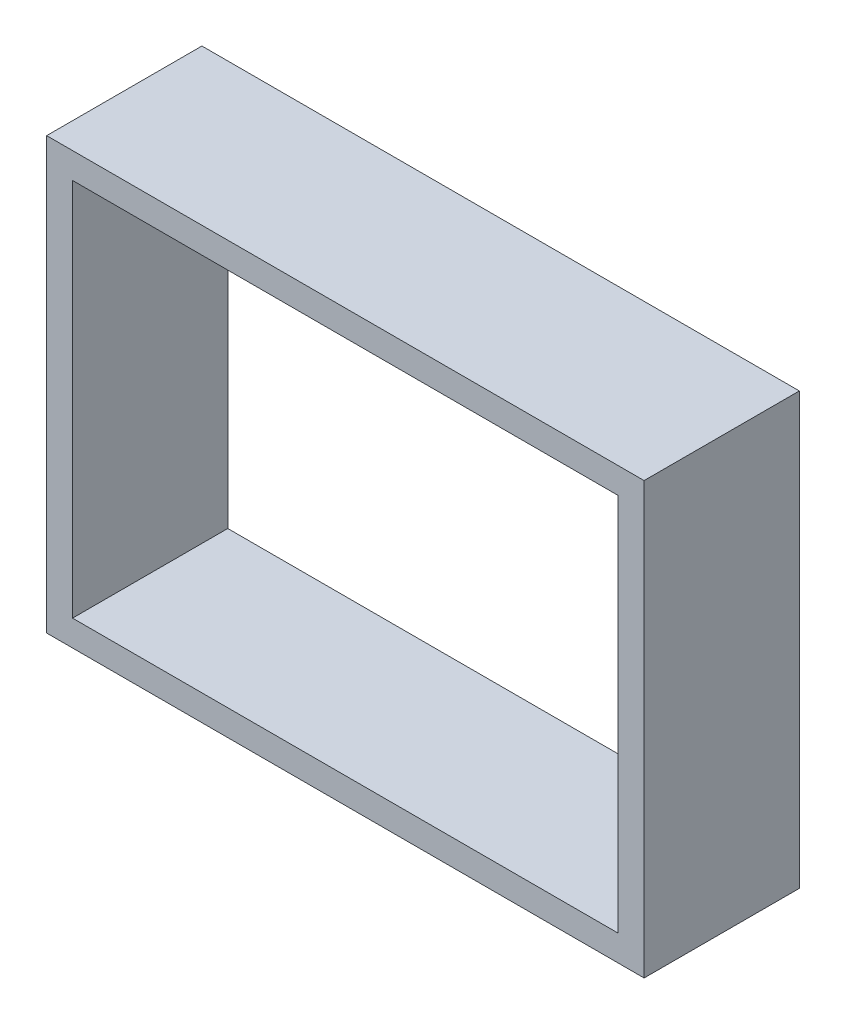
SolidWorks part; units mm, degrees
ref_plane "Alzado" through (0, 0, 0) normal (0, 0, 1) x (1, 0, 0)
ref_plane "Planta" through (0, 0, 0) normal (0, 1, 0) x (1, 0, 0)
ref_plane "Vista lateral" through (0, 0, 0) normal (1, 0, 0) x (0, 0, -1)
sketch "Croquis1" plane through (0, 0, 0) normal (0, 0, 1) x (1, 0, 0)
  line L0 (36.0507, -11.25) -> (-52.3115, -11.25) construction
  line L1 (36.0507, -11.25) -> (36.0507, 51.35) construction
  line L2 (-52.3115, -11.25) -> (-52.3115, 51.35) construction
  line L3 (36.0507, 51.35) -> (-52.3115, 51.35) construction
  line L4 (38.0507, -13.25) -> (-54.3115, -13.25)
  line L5 (-54.3115, -13.25) -> (-54.3115, 53.35)
  line L6 (38.0507, 53.35) -> (-54.3115, 53.35)
  line L7 (38.0507, -13.25) -> (38.0507, 53.35)
  line L8 (34.0507, -9.25) -> (-50.3115, -9.25)
  line L9 (-50.3115, -9.25) -> (-50.3115, 49.35)
  line L10 (34.0507, 49.35) -> (-50.3115, 49.35)
  line L11 (34.0507, -9.25) -> (34.0507, 49.35)
  line L12 (15.5, -9.25) -> (-18.5, -9.25) construction
  line L15 (18.5, 49.35) -> (15.5, 49.35) construction
  dimension "D3" = 0
  dimension "D5" = 0
  dimension "D1" = 2
  dimension "D2" = 2
extrude "Saliente-Extruir1" add sketch "Croquis1" against normal blind 23 and the other way blind 1
sketch "Croquis2" plane through (0, -13.25, 0) normal (0, -1, 0) x (-1, 0, 0)
  line L0 (48.7666, -1) -> (48.7666, 23) construction
  line L1 (54.3115, -1) -> (-38.0507, -1) construction
  line L2 (54.3115, 23) -> (-38.0507, 23) construction
  circle A0 centre (48.7666, 3.9048) radius 4
  point P8 (40.2124, 11)
  point P10 (40.2124, 11)
  point P12 (40.2124, 11)
  point P13 (0, 0)
  point P14 (40.2124, 11)
  point P15 (40.2124, 15.9869)
  point P16 (48.623, 18.296)
  point P17 (37.4355, 3.9048)
  point P18 (48.7666, 3.1819)
extrude "Cortar-Extruir1" cut sketch "Croquis2" against normal blind 2
